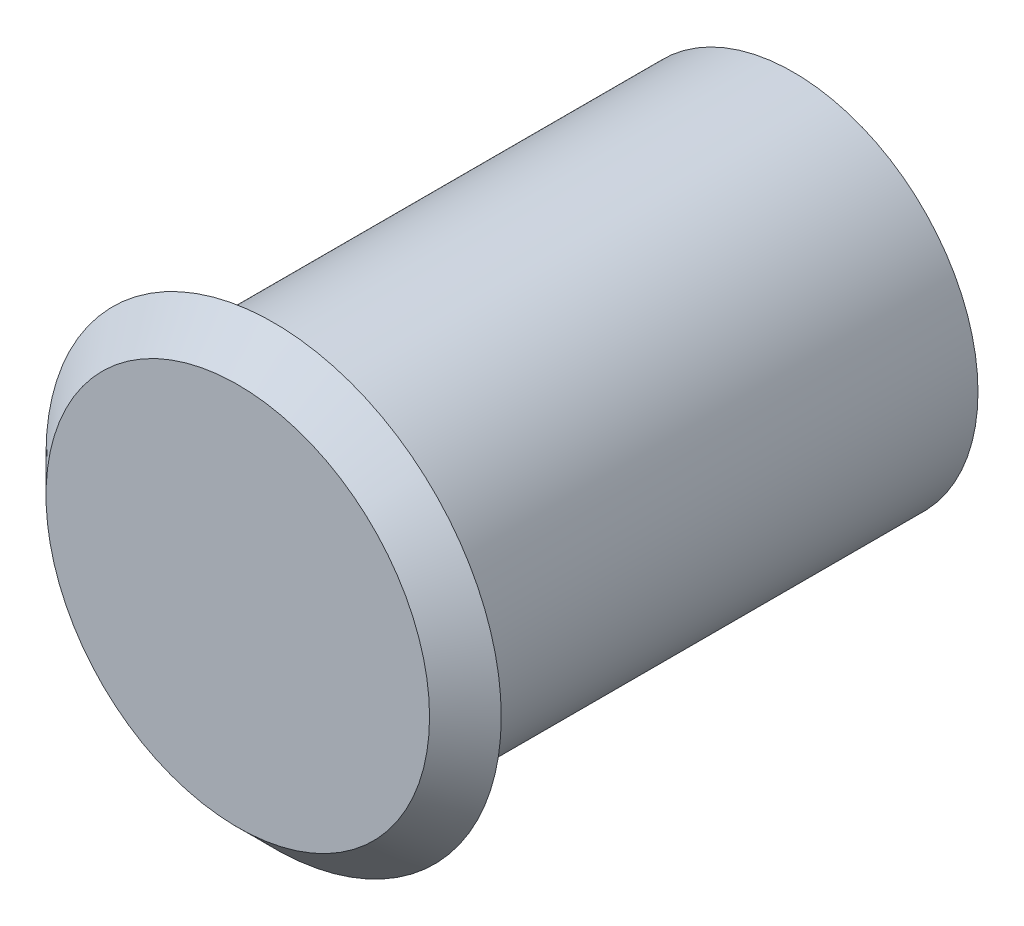
SolidWorks part; units mm, degrees
material "Custom Plastic"
ref_plane "X-Y Datum" through (0, 0, 0) normal (0, 0, 1) x (1, 0, 0)
ref_plane "X-Z Datum" through (0, 0, 0) normal (0, 1, 0) x (1, 0, 0)
ref_plane "Y-Z Datum" through (0, 0, 0) normal (1, 0, 0) x (0, 0, -1)
sketch "Sketch2" plane through (0, 0, 0) normal (0, 0, 1) x (1, 0, 0)
  circle A0 centre (0, 0) radius 10.3
  dimension "D1" = 20.6
extrude "Boss-Extrude1" add sketch "Sketch2" along normal blind 29
sketch "Sketch3" plane through (0, 0, 29) normal (0, 0, 1) x (1, 0, 0)
  circle A0 centre (0, 0) radius 12.7
  dimension "D1" = 25.4
extrude "Boss-Extrude2" add sketch "Sketch3" along normal blind 2
chamfer "Chamfer1" distance 2 angle 45 1 edges at (12.7, 0, 31)
